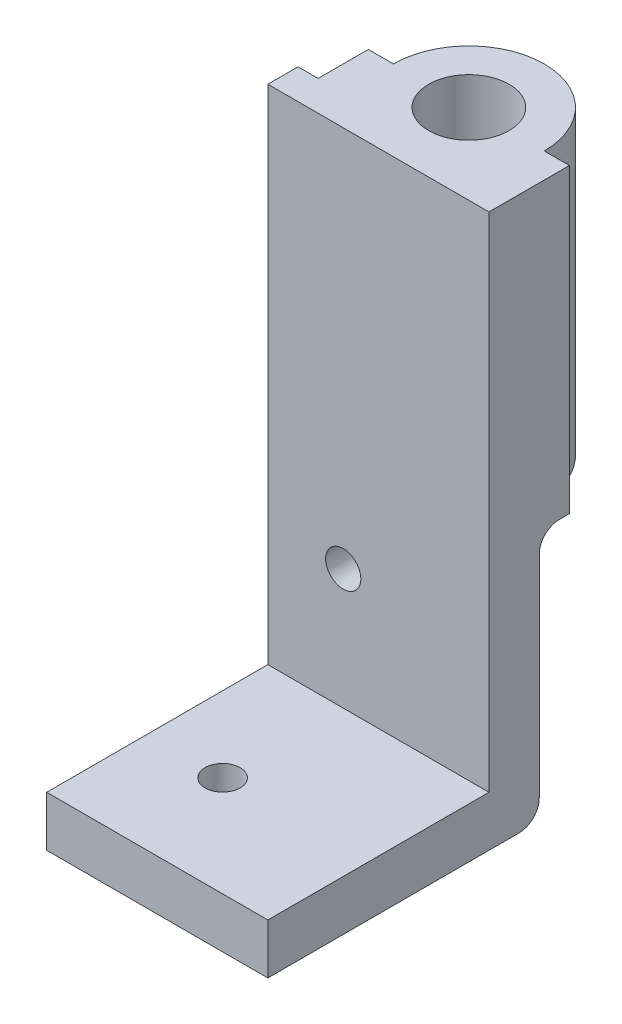
SolidWorks part; units mm, degrees
ref_plane "Front Plane" through (0, 0, 0) normal (0, 0, 1) x (1, 0, 0)
ref_plane "Top Plane" through (0, 0, 0) normal (0, 1, 0) x (1, 0, 0)
ref_plane "Right Plane" through (0, 0, 0) normal (1, 0, 0) x (0, 0, -1)
sketch "Sketch1" plane through (0, 0, 0) normal (0, 0, 1) x (1, 0, 0)
  line L1 (0, 0) -> (22, 0)
  line L2 (0, 0) -> (0, 53)
  line L3 (0, 53) -> (22, 53)
  line L4 (22, 0) -> (22, 53)
  dimension "D1" = 22
  dimension "D2" = 53
extrude "Boss-Extrude1" add sketch "Sketch1" along normal blind 3
sketch "Sketch2" plane through (0, 0, 3) normal (0, 0, 1) x (1, 0, 0)
  line L0 (0, 0) -> (22, 0) construction
  line L1 (22, 0) -> (0, 0)
  line L2 (22, 0) -> (22, 3)
  line L3 (22, 3) -> (0, 3)
  line L4 (0, 0) -> (0, 3)
  line L5 (0, 53) -> (0, 0) construction
  line L6 (22, 0) -> (22, 53) construction
  dimension "D1" = 3
extrude "Boss-Extrude2" add sketch "Sketch2" along normal blind 22
sketch "Sketch3" plane through (0, 0, 0) normal (0, -1, 0) x (1, 0, 0)
  line L0 (0, 0) -> (22, 0) construction
  line L1 (0, 25) -> (0, 0) construction
  circle A0 centre (7.5, 15) radius 1.75
  dimension "D1" = 3.5
  dimension "D2" = 15
  dimension "D3" = 7.5
extrude "Cut-Extrude1" cut sketch "Sketch3" against normal blind 22
sketch "Sketch4" plane through (0, 0, 0) normal (0, 0, -1) x (-1, 0, 0)
  line L0 (0, 0) -> (-22, 0) construction
  line L1 (0, 53) -> (0, 0) construction
  circle A0 centre (-7.5, 15) radius 1.75
  dimension "D1" = 3.5
  dimension "D2" = 15
  dimension "D3" = 7.5
extrude "Cut-Extrude2" cut sketch "Sketch4" against normal through all
sketch "Sketch5" plane through (0, 0, 0) normal (0, 0, -1) x (-1, 0, 0)
  line L0 (-22, 53) -> (0, 53) construction
  line L1 (-2, 53) -> (-22, 53)
  line L2 (-2, 53) -> (-2, 23)
  line L3 (-2, 23) -> (-22, 23)
  line L4 (-22, 53) -> (-22, 23)
  line L5 (0, 53) -> (0, 0) construction
  dimension "D1" = 30
  dimension "D2" = 20
  dimension "D3" = 2
extrude "Boss-Extrude3" add sketch "Sketch5" along normal blind 5
sketch "Sketch6" plane through (0, 23, 0) normal (0, -1, 0) x (1, 0, 0)
  line L0 (22, -5) -> (2, -5) construction
  line L1 (19.5, -5) -> (4.5, -5)
  arc A0 (4.5, -5) -> (19.5, -5) centre (12, -5) ccw
  dimension "D1" = 15
extrude "Boss-Extrude4" add sketch "Sketch6" against normal blind 30
sketch "Sketch7" plane through (0, 53, 0) normal (0, 1, 0) x (1, 0, 0)
  circle A0 centre (12, 5) radius 4
  arc A1 (19.5, 5) -> (4.5, 5) centre (12, 5) ccw construction
  dimension "D1" = 8
extrude "Cut-Extrude3" cut sketch "Sketch7" against normal blind 20
sketch "Sketch8" plane through (0, 0, 0) normal (0, 0, -1) x (-1, 0, 0)
  line L0 (0, 0) -> (-22, 0) construction
  line L1 (0, 0) -> (-22, 0)
  line L2 (0, 0) -> (0, 23)
  line L3 (0, 23) -> (-22, 23)
  line L4 (-22, 0) -> (-22, 23)
  line L5 (-22, 23) -> (-2, 23) construction
  line L6 (-22, 0) -> (-22, 23) construction
  line L7 (0, 53) -> (0, 0) construction
  circle A0 centre (-7.5, 15) radius 1.75
  circle A1 centre (-7.5, 15) radius 1.75 construction
  point P14 (-10.3803, 15)
  dimension "D1" = 3.5
extrude "Boss-Extrude5" add sketch "Sketch8" along normal blind 1
sketch "Sketch9" plane through (0, 0, 0) normal (0, -1, 0) x (1, 0, 0)
  line L0 (0, 25) -> (22, 25) construction
  line L1 (0, 25) -> (22, 25)
  line L2 (0, 25) -> (0, -1)
  line L3 (0, -1) -> (22, -1)
  line L4 (22, 25) -> (22, -1)
  line L5 (22, -1) -> (0, -1) construction
  line L6 (22, 25) -> (22, -1) construction
  line L7 (0, 25) -> (0, -1) construction
  circle A0 centre (7.5, 15) radius 1.75
  circle A1 centre (7.5, 15) radius 1.75 construction
  dimension "D1" = 3.5
extrude "Boss-Extrude6" add sketch "Sketch9" along normal blind 1
sketch "Sketch10" plane through (0, -1, 0) normal (0, -1, 0) x (-1, 0, 0)
  line L0 (0, -25) -> (0, 1) construction
  line L1 (0, -25) -> (-22, -25)
  line L2 (0, -25) -> (0, 1)
  line L3 (0, 1) -> (-22, 1)
  line L4 (-22, -25) -> (-22, 1)
  line L5 (-22, -25) -> (0, -25) construction
  line L6 (-22, 1) -> (-22, -25) construction
  line L7 (0, 1) -> (-22, 1) construction
  circle A0 centre (-7.5, -15) radius 1.75
  circle A1 centre (-7.5, -15) radius 1.75 construction
extrude "Boss-Extrude7" add sketch "Sketch10" along normal blind 1
sketch "Sketch11" plane through (0, 0, -1) normal (0, 0, -1) x (-1, 0, 0)
  line L0 (0, -2) -> (0, 23) construction
  line L1 (0, -2) -> (-22, -2)
  line L2 (0, -2) -> (0, 23)
  line L3 (0, 23) -> (-22, 23)
  line L4 (-22, -2) -> (-22, 23)
  line L5 (0, -2) -> (-22, -2) construction
  line L6 (-22, 23) -> (-22, -2) construction
  line L7 (-22, 23) -> (-2, 23) construction
  circle A0 centre (-7.5, 15) radius 1.75
  circle A1 centre (-7.5, 15) radius 1.75 construction
extrude "Boss-Extrude8" add sketch "Sketch11" along normal blind 1
fillet "Fillet1" radius 2 1 edges at (11, -2, -2)
fillet "Fillet2" radius 2 1 edges at (12, 23, -2)
